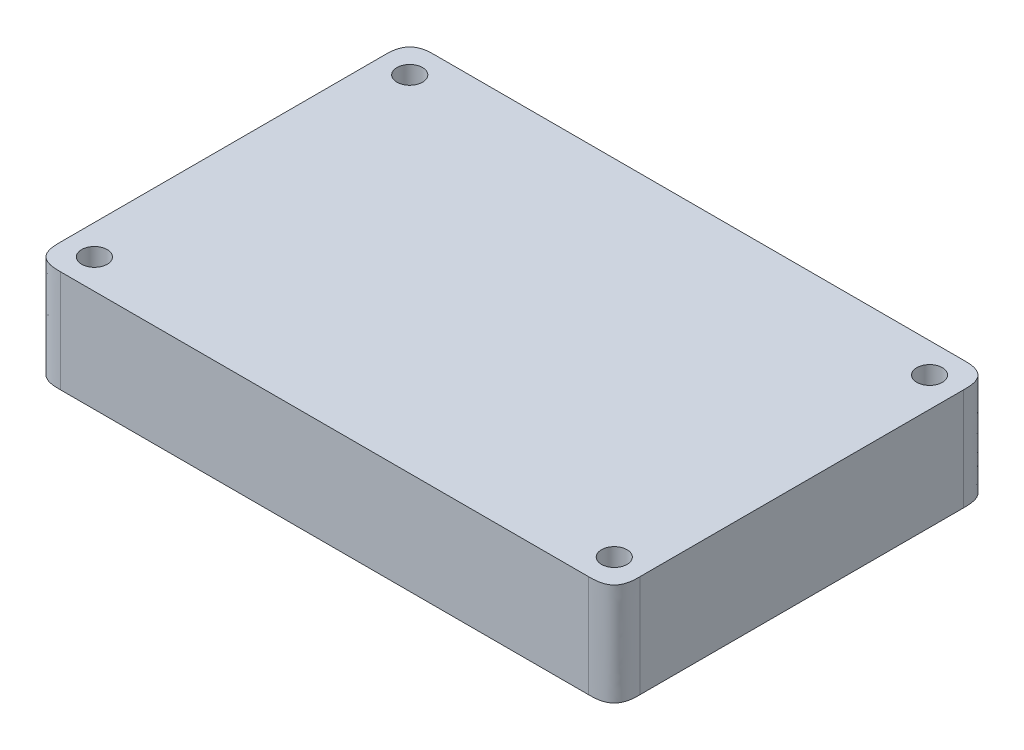
SolidWorks part; units mm, degrees
ref_plane "前视基准面" through (0, 0, 0) normal (0, 0, 1) x (1, 0, 0)
ref_plane "上视基准面" through (0, 0, 0) normal (0, 1, 0) x (1, 0, 0)
ref_plane "右视基准面" through (0, 0, 0) normal (1, 0, 0) x (0, 0, -1)
other "Configuration Table"
sketch "草图1" plane through (0, 0, 0) normal (0, 1, 0) x (1, 0, 0)
  line L0 (0, 0) -> (-31.5241, 0) construction
  line L1 (2.1418, 0) -> (2.1418, 32.6937) construction
  line L3 (-31.8582, 22) -> (36.1418, 22)
  line L4 (-31.8582, 22) -> (-31.8582, -22)
  line L5 (-31.8582, -22) -> (36.1418, -22)
  line L6 (36.1418, 22) -> (36.1418, -22)
  circle A0 centre (-28.3582, -18.5) radius 1.5
  circle A1 centre (32.6418, -18.5) radius 1.5
  circle A2 centre (32.6418, 18.5) radius 1.5
  circle A3 centre (-28.3582, 18.5) radius 1.5
  dimension "D3" = 3
  dimension "D1" = 44
  dimension "D2" = 68
  dimension "D4" = 18.5
  dimension "D5" = 30.5
extrude "凸台-拉伸1" add sketch "草图1" along normal blind 12
fillet "圆角1" radius 3 4 edges at (-31.8582, 6, -22) (36.1418, 6, -22) (-31.8582, 6, 22) (36.1418, 6, 22) curvature continuous yes
